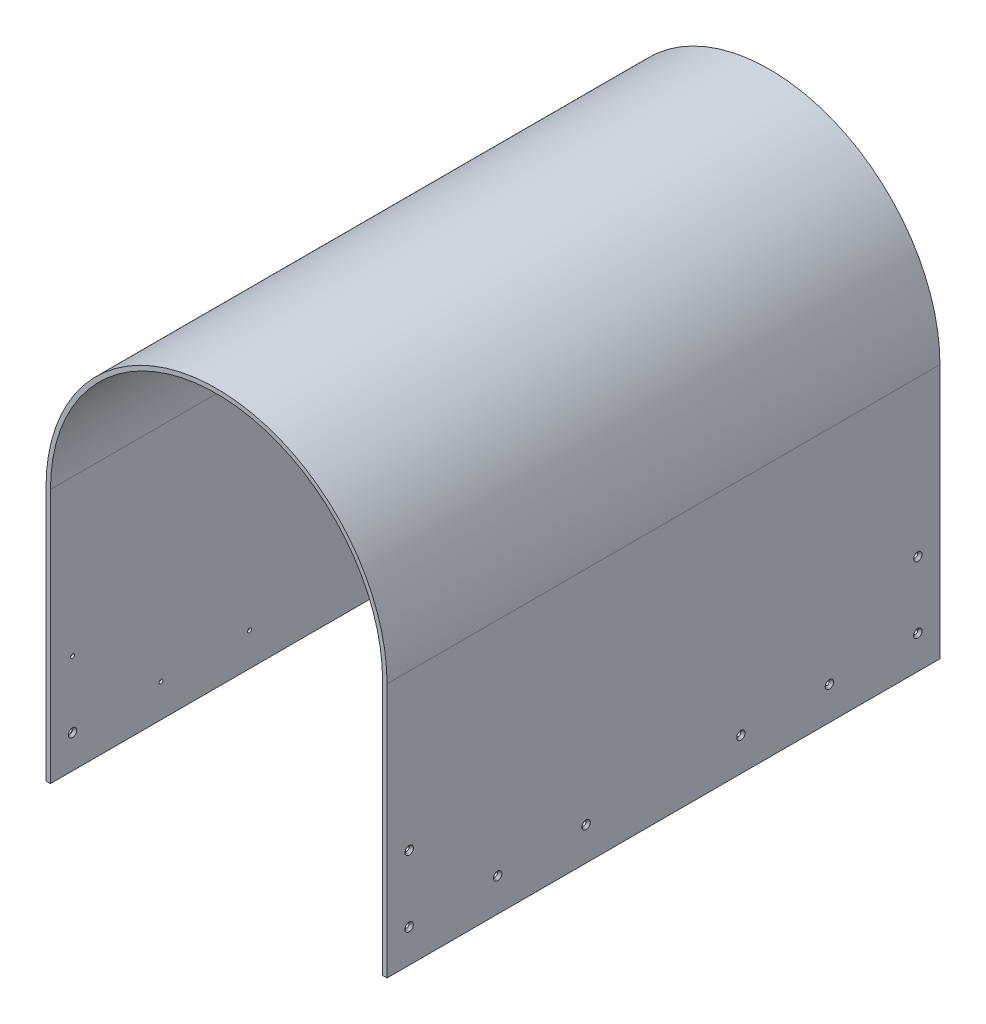
SolidWorks part; units mm, degrees
material "ABS PC"
ref_plane "Front Plane" through (0, 0, 0) normal (0, 0, 1) x (1, 0, 0)
ref_plane "Top Plane" through (0, 0, 0) normal (0, 1, 0) x (1, 0, 0)
ref_plane "Right Plane" through (0, 0, 0) normal (1, 0, 0) x (0, 0, -1)
sketch "Sketch1" plane through (0, 0, 0) normal (0, 0, 1) x (1, 0, 0)
  line L0 (0, 0) -> (0, 212.7728) construction
  line L1 (-75.1, 0) -> (-75.1, 115.2)
  line L2 (75.1, 0) -> (75.1, 115.2)
  line L7 (-26.8281, 0) -> (29.8493, 0) construction
  line L8 (-77.1, 0) -> (-77.1, 115.2)
  line L9 (77.1, 0) -> (77.1, 115.2)
  line L10 (-75.1, 0) -> (-77.1, 0)
  line L11 (75.1, 0) -> (77.1, 0)
  arc A2 (77.1, 115.2) -> (-77.1, 115.2) centre (0, 115.2) ccw
  arc A4 (75.1, 115.2) -> (-75.1, 115.2) centre (0, 115.2) ccw
  dimension "D4" = 75.1
  dimension "D2" = 150.2
  dimension "D3" = 115.2
  dimension "D1" = 2
extrude "Boss-Extrude1" add sketch "Sketch1" along normal mid plane 250
sketch "Sketch3" plane through (-77.1, 0, 0) normal (-1, 0, 0) x (0, 0, 1)
  line L0 (-125, 15) -> (125, 15) construction
  line L1 (-125, 115.2) -> (-125, 0) construction
  line L2 (125, 115.2) -> (125, 0) construction
  line L3 (125, 0) -> (-125, 0) construction
  circle A0 centre (-115, 15) radius 0.9
  circle A1 centre (-75, 15) radius 0.9
  circle A2 centre (-35, 15) radius 0.9
  circle A3 centre (-115, 45) radius 0.9
  dimension "D1" = 15
extrude "Cut-Extrude1" cut sketch "Sketch3" against normal through all
mirror "Mirror1" about plane through (0, 0, 0) normal (0, 0, 1) of "Cut-Extrude1"
chamfer "Chamfer1" distance 1 angle 45 9 edges at (-75.1, 15, 115.9) (-77.1, 15, 114.1) (-77.1, 45, 114.1) (-77.1, 15, 74.1) (-77.1, 15, 34.1) (-77.1, 15, -34.1) (-77.1, 15, -74.1) (-77.1, 15, -114.1) (-77.1, 45, -114.1)
chamfer "Chamfer2" distance 1 angle 45 8 edges at (77.1, 45, -114.1) (77.1, 15, -114.1) (77.1, 15, -74.1) (77.1, 15, -34.1) (77.1, 15, 34.1) (77.1, 15, 74.1) (77.1, 15, 114.1) (77.1, 45, 114.1)
